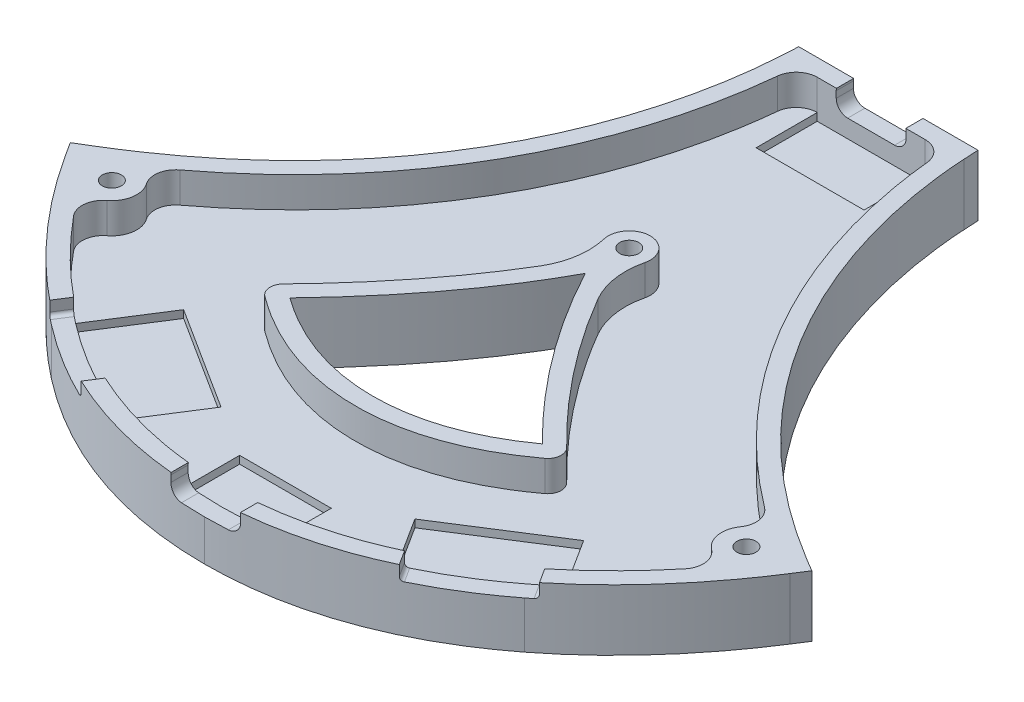
SolidWorks part; units mm, degrees
material "Default Heavy"
ref_plane "Front \"XY\"" through (0, 0, 0) normal (0, 0, 1) x (1, 0, 0)
ref_plane "Top \"XZ\"" through (0, 0, 0) normal (0, 1, 0) x (1, 0, 0)
ref_plane "Right \"YZ\"" through (0, 0, 0) normal (1, 0, 0) x (0, 0, -1)
sketch "Sketch5" plane through (0, 0, 0) normal (0, 1, 0) x (1, 0, 0)
  line L0 (11.8441, 37.7651) -> (11.7402, 39.6731)
  line L1 (11.7402, 39.6731) -> (-11.7315, 39.6731)
  line L2 (-11.7315, 39.6731) -> (-11.8354, 37.7651)
  line L3 (-46.7664, -17.8284) -> (-48.5396, -18.8969)
  line L4 (-48.5396, -18.8969) -> (-47.426, -20.6418)
  line L5 (47.433, -20.6463) -> (48.547, -18.9011)
  line L6 (48.547, -18.9011) -> (46.7735, -17.8326)
  line L7 (-6.0753, 35.6378) -> (7.9467, 35.6378)
  spline S0 degree 3 poles (46.7735, -17.8326) (17.0035, 0.1023) (12.4291, 27.0232) (11.8441, 37.7651) knots 0 0 0 0 1 1 1 1
  spline S1 degree 3 poles (-11.8354, 37.7651) (-12.42, 27.0256) (-16.9942, 0.1099) (-46.7664, -17.8284) knots 4 4 4 4 5 5 5 5
  spline S2 degree 3 poles (-47.426, -20.6418) (-44.2218, -25.663) (-38.764, -32.9144) (-30.9593, -38.9452) knots 7 7 7 7 8 8 8 8
  spline S3 degree 3 poles (-30.9593, -38.9452) (-21.5489, -46.2168) (-11.1312, -49.9039) (0.0044, -49.9039) knots 8 8 8 8 9 9 9 9
  spline S4 degree 3 poles (0.0044, -49.9039) (11.1376, -49.9039) (21.554, -46.2178) (30.9639, -38.9481) knots 9 9 9 9 10 10 10 10
  spline S5 degree 3 poles (30.9639, -38.9481) (38.7697, -32.9178) (44.2283, -25.667) (47.433, -20.6463) knots 10 10 10 10 11 11 11 11
  spline S6 degree 3 poles (-26.2671, -37.4303) (-33.7735, -32.2159) (-39.286, -25.5238) (-42.8998, -20.1821) knots 6 6 6 6 7 7 7 7
  spline S7 degree 3 poles (-21.0273, -20.9114) (-25.95, -25.8342) (-27.72, -31.5456) (-26.2671, -37.4303) knots 5 5 5 5 6 6 6 6
  spline S8 degree 3 poles (-2.2272, 4.5048) (-6.4059, -4.0601) (-12.7224, -12.6065) (-21.0273, -20.9114) knots 4 4 4 4 5 5 5 5
  spline S9 degree 3 poles (-4.959, 11.1576) (-4.2007, 9.0673) (-3.2985, 6.8364) (-2.2272, 4.5048) knots 3 3 3 3 4 4 4 4
  spline S10 degree 3 poles (-9.1537, 27.2693) (-8.3696, 22.4813) (-7.0743, 16.988) (-4.959, 11.1576) knots 2 2 2 2 3 3 3 3
  spline S11 degree 3 poles (-14.8927, 10.4237) (-11.9606, 16.4408) (-10.1982, 22.2166) (-9.1537, 27.2693) knots 1 1 1 1 2 2 2 2
  spline S12 degree 3 poles (-42.8998, -20.1821) (-30.3262, -12.2114) (-20.909, -1.9228) (-14.8927, 10.4237) knots 0 0 0 0 1 1 1 1
  spline S13 degree 3 poles (0, 0) (3.7422, -7.0613) (9.039, -14.7607) (16.5263, -22.1536) knots 3 3 3 3 4 4 4 4
  spline S14 degree 3 poles (-16.5604, -22.1226) (-9.5786, -14.8948) (-4.0267, -7.4755) (0, 0) knots 2 2 2 2 3 3 3 3
  spline S15 degree 3 poles (16.5263, -22.1536) (11.2873, -25.9276) (5.7395, -27.8446) (0.0044, -27.8446) (-5.7464, -27.8446) (-11.3088, -25.9169) (-16.5604, -22.1226) knots 0 0 0 0 1 1 1 2 2 2 2
  spline S16 degree 3 poles (30.8834, -33.8552) (23.2458, -40.4324) (13.0017, -45.8687) (0.0044, -45.8687) (-7.8162, -45.8687) (-14.6395, -43.9001) (-20.4984, -40.8995) knots 4 4 4 4 5 5 5 6 6 6 6
  spline S17 degree 3 poles (19.51, -24.974) (22.8871, -28.0328) (26.6618, -31.0165) (30.8834, -33.8552) knots 3 3 3 3 4 4 4 4
  spline S18 degree 3 poles (-19.372, -25.0702) (-13.2945, -29.589) (-6.7848, -31.8798) (0.0044, -31.8798) (6.8416, -31.8798) (13.3956, -29.5569) (19.51, -24.974) knots 1 1 1 1 2 2 2 3 3 3 3
  spline S19 degree 3 poles (-20.4984, -40.8995) (-23.8177, -35.2119) (-23.4372, -29.8962) (-19.372, -25.0702) knots 0 0 0 0 1 1 1 1
  spline S20 degree 3 poles (33.9362, -31.0385) (13.0256, -17.2626) (3.31, 0.1969) (-1.1657, 12.5337) knots 0 0 0 0 1 1 1 1
  spline S21 degree 3 poles (-1.1657, 12.5337) (-4.4547, 21.5995) (-5.6698, 29.8082) (-6.0753, 35.6378) knots 1 1 1 1 2 2 2 2
  spline S22 degree 3 poles (7.9467, 35.6378) (8.4835, 29.2105) (10.1709, 20.1275) (14.8992, 10.4216) knots 3 3 3 3 4 4 4 4
  spline S23 degree 3 poles (14.8992, 10.4216) (20.9146, -1.9265) (30.3319, -12.2156) (42.9069, -20.1863) knots 4 4 4 4 5 5 5 5
  spline S24 degree 3 poles (42.9069, -20.1863) (40.659, -23.5082) (37.6756, -27.3523) (33.9362, -31.0385) knots 5 5 5 5 6 6 6 6
sketch "Sketch10" plane through (0, 0, 0) normal (0, 1, 0) x (1, 0, 0)
  line L0 (48.547, -18.9011) -> (46.7735, -17.8326) construction
  line L1 (47.433, -20.6463) -> (48.547, -18.9011) construction
  line L2 (-48.5396, -18.8969) -> (-47.426, -20.6418) construction
  line L3 (-46.7664, -17.8284) -> (-48.5396, -18.8969) construction
  line L4 (-11.7315, 39.6731) -> (-11.8354, 37.7651) construction
  line L5 (11.7402, 39.6731) -> (-11.7315, 39.6731) construction
  line L6 (11.8441, 37.7651) -> (11.7402, 39.6731) construction
  line L14 (48.547, -18.9011) -> (46.7735, -17.8326)
  line L15 (47.433, -20.6463) -> (48.547, -18.9011)
  line L16 (-48.5396, -18.8969) -> (-47.426, -20.6418)
  line L17 (-46.7664, -17.8284) -> (-48.5396, -18.8969)
  line L18 (-11.7315, 39.6731) -> (-11.8354, 37.7651)
  line L19 (11.7402, 39.6731) -> (-11.7315, 39.6731)
  line L20 (11.8441, 37.7651) -> (11.7402, 39.6731)
  spline S0 degree 3 poles (-656.5291, 1825.394) (211.0906, -2141.3129) (197.0374, 2116.559) (-250.135, -1997.4745) knots 1.9887 1.9887 1.9887 1.9887 18.868565 18.868565 18.868565 18.868565 only from (30.9639, -38.9481) to (47.433, -20.6463) construction
  spline S1 degree 3 poles (-182.7302, 1911.4069) (-625.9753, -969.181) (972.7294, -384.9371) (-706.3522, 1782.3273) knots -3.602256 -3.602256 -3.602256 -3.602256 22.781955 22.781955 22.781955 22.781955 only from (0.0044, -49.9039) to (30.9639, -38.9481) construction
  spline S2 degree 3 poles (706.2836, 1782.3794) (-972.1545, -384.1805) (624.8527, -969.872) (184.0184, 1911.3649) knots -4.782528 -4.782528 -4.782528 -4.782528 21.598996 21.598996 21.598996 21.598996 only from (-30.9593, -38.9452) to (0.0044, -49.9039) construction
  spline S3 degree 3 poles (250.1669, -1997.4323) (-197.0811, 2116.5675) (-210.9874, -2141.3429) (656.3732, 1825.4364) knots -0.86853 -0.86853 -0.86853 -0.86853 16.011373 16.011373 16.011373 16.011373 only from (-47.426, -20.6418) to (-30.9593, -38.9452) construction
  spline S4 degree 3 poles (885.5961, -1747.6701) (-1144.1453, 1780.0004) (1414.1117, -1430.9185) (-1803.61, 911.43) knots 0.325017 0.325017 0.325017 0.325017 8.201625 8.201625 8.201625 8.201625 only from (-11.8354, 37.7651) to (-46.7664, -17.8284) construction
  spline S5 degree 3 poles (1803.2949, 912.0011) (-1413.7247, -1431.4451) (1143.7595, 1780.3831) (-885.202, -1747.8751) knots -3.201509 -3.201509 -3.201509 -3.201509 4.674641 4.674641 4.674641 4.674641 only from (46.7735, -17.8326) to (11.8441, 37.7651) construction
  spline S6 degree 3 poles (30.9639, -38.9481) (38.7697, -32.9178) (44.2283, -25.667) (47.433, -20.6463) knots 10 10 10 10 11 11 11 11
  spline S7 degree 3 poles (0.0044, -49.9039) (11.1376, -49.9039) (21.554, -46.2178) (30.9639, -38.9481) knots 9 9 9 9 10 10 10 10
  spline S8 degree 3 poles (-30.9593, -38.9452) (-21.5489, -46.2168) (-11.1312, -49.9039) (0.0044, -49.9039) knots 8 8 8 8 9 9 9 9
  spline S9 degree 3 poles (-47.426, -20.6418) (-44.2218, -25.663) (-38.764, -32.9144) (-30.9593, -38.9452) knots 7 7 7 7 8 8 8 8
  spline S10 degree 3 poles (-11.8354, 37.7651) (-12.42, 27.0256) (-16.9942, 0.1099) (-46.7664, -17.8284) knots 4 4 4 4 5 5 5 5
  spline S11 degree 3 poles (46.7735, -17.8326) (17.0035, 0.1023) (12.4291, 27.0232) (11.8441, 37.7651) knots 0 0 0 0 1 1 1 1
  spline S12 degree 3 poles (-812.1216, 1751.0499) (153.3939, 718.8091) (113.1908, -27.8446) (0.0044, -27.8446) (-113.2755, -27.8446) (-153.4167, 720.1128) (813.7688, 1750.0629) knots -18.735656 -18.735656 -18.735656 -18.735656 1 1 1 20.698036 20.698036 20.698036 20.698036 only from (16.5263, -22.1536) to (-16.5604, -22.1226) construction
  spline S13 degree 3 poles (-656.972, -1887.5112) (895.1742, 1891.164) (-1266.5252, -1556.179) (1736.0801, 959.1971) knots -9.517328 -9.517328 -9.517328 -9.517328 14.561888 14.561888 14.561888 14.561888 only from (0, 0) to (16.5263, -22.1536) construction
  spline S14 degree 3 poles (-1494.9401, 1101.9266) (-493.0371, -1467.4363) (1527.6763, 1113.0775) (-1935.6902, -378.8535) knots -19.400052 -19.400052 -19.400052 -19.400052 21.459168 21.459168 21.459168 21.459168 only from (-16.5604, -22.1226) to (0, 0) construction
  spline S15 degree 3 poles (16.5263, -22.1536) (11.2873, -25.9276) (5.7395, -27.8446) (0.0044, -27.8446) (-5.7464, -27.8446) (-11.3088, -25.9169) (-16.5604, -22.1226) knots 0 0 0 0 1 1 1 2 2 2 2
  spline S16 degree 3 poles (0, 0) (3.7422, -7.0613) (9.039, -14.7607) (16.5263, -22.1536) knots 3 3 3 3 4 4 4 4
  spline S17 degree 3 poles (-16.5604, -22.1226) (-9.5786, -14.8948) (-4.0267, -7.4755) (0, 0) knots 2 2 2 2 3 3 3 3
extrude "Boss-Extrude4" add sketch "Sketch10" along normal blind 3
hole_wizard "CBORE for M1.6 SHCS1" [suppressed] positions "Sketch13" profile "Sketch15" counterbore size "M1.6" standard "ANSI Metric"
sketch "Sketch13" plane through (0, 0, 0) normal (0, -1, 0) x (-1, 0, 0)
  point P0 (0, 3.0473)
  point P4 (0, -16.1117)
sketch "Sketch15" plane through (0, 0, -3.0473) normal (1, 0, 0) x (0, 0, -1)
  line L0 (0, 0) -> (0, 3)
  line L1 (0, 3) -> (0.9, 3)
  line L3 (0.9, 3) -> (0.9, 1.6)
  line L4 (0.9, 1.6) -> (1.75, 1.6)
  line L5 (1.75, 1.6) -> (1.75, 0)
  line L7 (1.75, 0) -> (0, 0)
  line L11 (0, -6.35) -> (0, 107.95) construction
  dimension "Thru Hole Dia." = 1.8
  dimension "Thru Hole Depth" = 3
  dimension "C'Bore Dia." = 3.5
  dimension "C'Bore Depth" = 1.6
sketch "Sketch16" plane through (0, 0, 0) normal (0, -1, 0) x (1, 0, 0)
  line L0 (0, 0) -> (0, 8.6371) construction
  line L2 (11.7402, -39.6731) -> (-11.7315, -39.6731) construction
  circle A0 centre (-41.547, 20.4011) radius 3.25
  circle A1 centre (41.547, 20.4011) radius 3.25
  circle A2 centre (0, -32.6731) radius 3.25
  circle A3 centre (0, 42.9039) radius 3.25
  dimension "D1" = 6.5
  dimension "D5" = 7
  dimension "D2" = 7
  dimension "D3" = 7
  dimension "D4" = 1.5
extrude "Cut-Extrude1" cut sketch "Sketch16" against normal blind 1.5
sketch "Sketch17" plane through (0, 3, 0) normal (0, 1, 0) x (1, 0, 0)
  line L0 (-45.0383, -19.5892) -> (-45.1073, -19.6307)
  line L1 (-45.1073, -19.6307) -> (-45.1073, -19.6307)
  line L2 (45.1144, -19.635) -> (45.1144, -19.635)
  line L3 (45.1144, -19.635) -> (45.0454, -19.5934)
  line L4 (9.4815, 37.0144) -> (9.4674, 37.2731)
  line L6 (-9.4586, 37.2731) -> (-9.4727, 37.0143)
  line L7 (47.433, -20.6463) -> (48.547, -18.9011) construction
  line L8 (-48.5396, -18.8969) -> (-47.426, -20.6418) construction
  line L9 (-46.7664, -17.8284) -> (-48.5396, -18.8969) construction
  line L10 (-11.7315, 39.6731) -> (-11.8354, 37.7651) construction
  line L11 (11.7402, 39.6731) -> (-11.7315, 39.6731) construction
  line L12 (11.8441, 37.7651) -> (11.7402, 39.6731) construction
  line L13 (48.547, -18.9011) -> (46.7735, -17.8326) construction
  line L14 (9.4674, 37.2731) -> (-9.4586, 37.2731) construction
  line L16 (47.433, -20.6463) -> (48.547, -18.9011)
  line L17 (-48.5396, -18.8969) -> (-47.426, -20.6418)
  line L18 (-46.7664, -17.8284) -> (-48.5396, -18.8969)
  line L19 (-11.7315, 39.6731) -> (-11.8354, 37.7651)
  line L20 (11.7402, 39.6731) -> (-11.7315, 39.6731)
  line L21 (11.8441, 37.7651) -> (11.7402, 39.6731)
  line L22 (48.547, -18.9011) -> (46.7735, -17.8326)
  line L23 (46.7735, -17.8326) -> (11.8441, 37.7651) construction
  line L24 (45.0454, -19.5934) -> (9.4815, 37.0144) construction
  line L25 (30.9639, -38.9481) -> (47.433, -20.6463) construction
  line L26 (29.588, -36.8891) -> (45.1144, -19.635) construction
  line L27 (0.0044, -49.9039) -> (30.9639, -38.9481) construction
  line L28 (0.0044, -47.3581) -> (29.588, -36.8891) construction
  line L29 (-30.9593, -38.9452) -> (0.0044, -49.9039) construction
  line L30 (-29.5833, -36.8863) -> (0.0044, -47.3581) construction
  line L31 (-47.426, -20.6418) -> (-30.9593, -38.9452) construction
  line L32 (-45.1073, -19.6307) -> (-29.5833, -36.8863) construction
  line L33 (-11.8354, 37.7651) -> (-46.7664, -17.8284) construction
  line L34 (-9.4727, 37.0143) -> (-45.0383, -19.5892) construction
  line L37 (7.0683, 37.4231) -> (-7.0595, 37.4231)
  line L38 (7.0683, 37.4231) -> (-7.0595, 37.4231)
  arc A42 (-38.2805, -14.817) -> (-38.8778, -18.5904) centre (-36.6252, -17.013) ccw
  arc A43 (-39.572, -23.0411) -> (-38.8778, -18.5904) centre (-41.54, -20.4546) ccw
  arc A44 (-39.572, -23.0411) -> (-40.0245, -26.984) centre (-37.9068, -25.2296) ccw
  arc A45 (40.0303, -26.9881) -> (39.5783, -23.0452) centre (37.9129, -25.2335) ccw
  arc A46 (38.8843, -18.595) -> (39.5783, -23.0452) centre (41.5466, -20.459) ccw
  arc A47 (38.8843, -18.595) -> (38.2869, -14.8218) centre (36.6316, -17.0178) ccw
  arc A48 (9.8049, 34.9434) -> (7.0683, 37.4231) centre (7.0683, 34.6731) ccw
  arc A49 (-7.0595, 37.4231) -> (-9.7962, 34.9434) centre (-7.0595, 34.6731) ccw
  arc A50 (-38.2805, -14.817) -> (-38.8778, -18.5904) centre (-36.6252, -17.013) ccw
  arc A51 (-39.572, -23.0411) -> (-38.8778, -18.5904) centre (-41.54, -20.4546) ccw
  arc A52 (-39.572, -23.0411) -> (-40.0245, -26.984) centre (-37.9068, -25.2296) ccw
  arc A53 (40.0303, -26.9881) -> (39.5783, -23.0452) centre (37.9129, -25.2335) ccw
  arc A54 (38.8843, -18.595) -> (39.5783, -23.0452) centre (41.5466, -20.459) ccw
  arc A55 (38.8843, -18.595) -> (38.2869, -14.8218) centre (36.6316, -17.0178) ccw
  arc A56 (9.8049, 34.9434) -> (7.0683, 37.4231) centre (7.0683, 34.6731) ccw
  arc A57 (-7.0595, 37.4231) -> (-9.7962, 34.9434) centre (-7.0595, 34.6731) ccw
  arc A60 (-18.5797, -20.9745) -> (-18.348, -23.6073) centre (-17.321, -22.1903) ccw
  arc A61 (18.3239, -23.6323) -> (18.5285, -20.9686) centre (17.2989, -22.2139) ccw
  arc A62 (2.674, 5.108) -> (3.7352, -2.0849) centre (12.1546, 2.832) ccw
  arc A63 (2.674, 5.108) -> (-2.6765, 5.1183) centre (0, 5.75) ccw
  arc A64 (-3.8051, -2.1373) -> (-2.6765, 5.1183) centre (-12.1658, 2.8788) ccw
  arc A65 (-18.5797, -20.9745) -> (-18.348, -23.6073) centre (-17.321, -22.1903) ccw
  arc A66 (18.3239, -23.6323) -> (18.5285, -20.9686) centre (17.2989, -22.2139) ccw
  arc A67 (2.674, 5.108) -> (3.7352, -2.0849) centre (12.1546, 2.832) ccw
  arc A68 (2.674, 5.108) -> (-2.6765, 5.1183) centre (0, 5.75) ccw
  arc A69 (-3.8051, -2.1373) -> (-2.6765, 5.1183) centre (-12.1658, 2.8788) ccw
  spline S6 degree 3 poles (-656.5291, 1825.394) (211.0906, -2141.3129) (197.0374, 2116.559) (-250.135, -1997.4745) knots 1.9887 1.9887 1.9887 1.9887 18.868565 18.868565 18.868565 18.868565 only from (30.9639, -38.9481) to (47.433, -20.6463) construction
  spline S7 degree 3 poles (-182.7302, 1911.4069) (-625.9753, -969.181) (972.7294, -384.9371) (-706.3522, 1782.3273) knots -3.602256 -3.602256 -3.602256 -3.602256 22.781955 22.781955 22.781955 22.781955 only from (0.0044, -49.9039) to (30.9639, -38.9481) construction
  spline S8 degree 3 poles (706.2836, 1782.3794) (-972.1545, -384.1805) (624.8527, -969.872) (184.0184, 1911.3649) knots -4.782528 -4.782528 -4.782528 -4.782528 21.598996 21.598996 21.598996 21.598996 only from (-30.9593, -38.9452) to (0.0044, -49.9039) construction
  spline S9 degree 3 poles (250.1669, -1997.4323) (-197.0811, 2116.5675) (-210.9874, -2141.3429) (656.3732, 1825.4364) knots -0.86853 -0.86853 -0.86853 -0.86853 16.011373 16.011373 16.011373 16.011373 only from (-47.426, -20.6418) to (-30.9593, -38.9452) construction
  spline S10 degree 3 poles (885.5961, -1747.6701) (-1144.1453, 1780.0004) (1414.1117, -1430.9185) (-1803.61, 911.43) knots 0.325017 0.325017 0.325017 0.325017 8.201625 8.201625 8.201625 8.201625 only from (-11.8354, 37.7651) to (-46.7664, -17.8284) construction
  spline S11 degree 3 poles (1803.2949, 912.0011) (-1413.7247, -1431.4451) (1143.7595, 1780.3831) (-885.202, -1747.8751) knots -3.201509 -3.201509 -3.201509 -3.201509 4.674641 4.674641 4.674641 4.674641 only from (46.7735, -17.8326) to (11.8441, 37.7651) construction
  spline S18 degree 3 poles (-8502.8403, -15893.4352) (-45.3248, 163.6482) (-63.6079, 7.9202) (-16.9995, -24.5656) (-16.6575, -24.7958) (-15.6219, -25.4682) (-14.9188, -25.892) (-12.7682, -27.0849) (-11.2799, -27.7756) (-8.9522, -28.6296) (-8.1568, -28.8845) (-6.5604, -29.3207) (-5.7573, -29.503) (-3.3327, -29.9425) (-1.6963, -30.092) (0.7891, -30.0958) (1.6234, -30.0599) (3.2688, -29.9148) (4.0842, -29.8058) (6.5087, -29.3724) (8.0964, -28.9415) (10.4366, -28.0907) (11.2058, -27.7741) (12.7076, -27.0863) (13.4428, -26.7142) (14.8841, -25.9177) (15.5903, -25.4934) (16.6293, -24.8206) (16.9723, -24.5902) (63.7168, 7.9132) (43.0919, 160.7438) (8908.8285, -15669.934) knots -4.23549 -4.23549 -4.23549 -4.23549 0.03125 0.03125 0.0625 0.0625 0.125 0.125 0.25 0.25 0.3125 0.3125 0.375 0.375 0.5 0.5 0.5625 0.5625 0.625 0.625 0.75 0.75 0.8125 0.8125 0.875 0.875 0.9375 0.9375 0.96875 0.96875 5.237555 5.237555 5.237555 5.237555 only from (-18.348, -23.6073) to (18.3239, -23.6323)
  spline S19 degree 3 poles (-12741.1091, -12700.2374) (334.5389, -8.3643) (90.0879, -95.516) (15.7148, -18.1086) (15.0318, -17.374) (13.0192, -15.1354) (11.7285, -13.5998) (-271.5891, 347.605) (2349.0319, 2696.4064) (15492.6273, 8956.8904) knots -13.129152 -13.129152 -13.129152 -13.129152 0.125 0.125 0.25 0.25 0.5 0.5 57.436471 57.436471 57.436471 57.436471 only from (18.5285, -20.9686) to (3.7352, -2.0849)
  spline S20 degree 3 poles (-17058.6487, 5589.1782) (-397.9032, 918.6322) (143.7118, 183.0534) (-11.892, -13.5529) (-13.1768, -15.0838) (-15.1614, -17.3294) (-15.8326, -18.0695) (-96.5644, -104.9378) (-336.1354, -50.3454) (13236.7022, -12181.1124) knots -30.580141 -30.580141 -30.580141 -30.580141 0.5 0.5 0.75 0.75 0.875 0.875 15.584267 15.584267 15.584267 15.584267 only from (-3.8051, -2.1373) to (-18.5797, -20.9745)
  spline S21 degree 3 poles (-18.348, -23.6073) (-18.0127, -23.8503) (-17.6773, -24.0932) (-16.9995, -24.5656) (-16.6575, -24.7958) (-15.6219, -25.4682) (-14.9188, -25.892) (-12.7682, -27.0849) (-11.2799, -27.7756) (-8.9522, -28.6296) (-8.1568, -28.8845) (-6.5604, -29.3207) (-5.7573, -29.503) (-3.3327, -29.9425) (-1.6963, -30.092) (0.7891, -30.0958) (1.6234, -30.0599) (3.2688, -29.9148) (4.0842, -29.8058) (6.5087, -29.3724) (8.0964, -28.9415) (10.4366, -28.0907) (11.2058, -27.7741) (12.7076, -27.0863) (13.4428, -26.7142) (14.8841, -25.9177) (15.5903, -25.4934) (16.6293, -24.8206) (16.9723, -24.5902) (17.6517, -24.1178) (17.9878, -23.8751) (18.3239, -23.6323) knots 0 0 0 0 0.03125 0.03125 0.0625 0.0625 0.125 0.125 0.25 0.25 0.3125 0.3125 0.375 0.375 0.5 0.5 0.5625 0.5625 0.625 0.625 0.75 0.75 0.8125 0.8125 0.875 0.875 0.9375 0.9375 0.96875 0.96875 1 1 1 1
  spline S22 degree 3 poles (18.5285, -20.9686) (17.8145, -20.2637) (17.1045, -19.555) (15.7148, -18.1086) (15.0318, -17.374) (13.0192, -15.1354) (11.7285, -13.5998) (8.0128, -8.8627) (5.7595, -5.5511) (3.7352, -2.0849) knots 0 0 0 0 0.125 0.125 0.25 0.25 0.5 0.5 1 1 1 1
  spline S23 degree 3 poles (-3.8051, -2.1373) (-5.8639, -5.5689) (-8.1671, -8.8465) (-11.892, -13.5529) (-13.1768, -15.0838) (-15.1614, -17.3294) (-15.8326, -18.0695) (-17.1931, -19.5335) (-17.8849, -20.2553) (-18.5797, -20.9745) knots 0 0 0 0 0.5 0.5 0.75 0.75 0.875 0.875 1 1 1 1
  spline S24 degree 3 poles (30.9639, -38.9481) (38.7697, -32.9178) (44.2283, -25.667) (47.433, -20.6463) knots 10 10 10 10 11 11 11 11
  spline S25 degree 3 poles (0.0044, -49.9039) (11.1376, -49.9039) (21.554, -46.2178) (30.9639, -38.9481) knots 9 9 9 9 10 10 10 10
  spline S26 degree 3 poles (-30.9593, -38.9452) (-21.5489, -46.2168) (-11.1312, -49.9039) (0.0044, -49.9039) knots 8 8 8 8 9 9 9 9
  spline S27 degree 3 poles (-47.426, -20.6418) (-44.2218, -25.663) (-38.764, -32.9144) (-30.9593, -38.9452) knots 7 7 7 7 8 8 8 8
  spline S28 degree 3 poles (-11.8354, 37.7651) (-12.42, 27.0256) (-16.9942, 0.1099) (-46.7664, -17.8284) knots 4 4 4 4 5 5 5 5
  spline S29 degree 3 poles (46.7735, -17.8326) (17.0035, 0.1023) (12.4291, 27.0232) (11.8441, 37.7651) knots 0 0 0 0 1 1 1 1
  spline S30 degree 3 poles (-1185.458, -17971.1401) (732.7038, 1486.4598) (-227.1134, 155.6968) (126.3209, -190.4314) (1044.5984, 512.9613) (11833.1848, 13466.1097) knots -54.647972 -54.647972 -54.647972 -54.647972 0.5 0.5 46.852212 46.852212 46.852212 46.852212 only from (-40.0245, -26.984) to (-29.5836, -37.1648)
  spline S31 degree 3 poles (-10552.0267, -14577.9353) (551.6703, 1727.3625) (-240.731, 80.6268) (-20.5651, -42.9151) (-18.1378, -44.0356) (-13.0925, -45.8527) (-10.5261, -46.5302) (665.8325, -163.4732) (3949.6007, 14900.1764) (343.1731, -10110.3603) knots -23.042965 -23.042965 -23.042965 -23.042965 0.25 0.25 0.5 0.5 0.75 0.75 65.44657 65.44657 65.44657 65.44657 only from (-29.5836, -37.1648) to (0.0044, -47.6539)
  spline S32 degree 3 poles (498.348, -17908.4467) (-1031.6717, 3878.1158) (-337.2571, -107.1241) (10.6298, -46.5101) (13.1926, -45.8231) (16.9224, -44.4744) (18.1468, -43.9718) (20.5589, -42.863) (21.7488, -42.2556) (241.5188, 81.0938) (-552.0997, 1742.02) (10508.6827, -14611.7053) knots -32.427338 -32.427338 -32.427338 -32.427338 0.25 0.25 0.5 0.5 0.625 0.625 0.75 0.75 24.161666 24.161666 24.161666 24.161666 only from (0.0044, -47.6539) to (29.5883, -37.1675)
  spline S33 degree 3 poles (-4432.1105, 17338.2057) (-1006.9632, 428.8583) (-119.8702, -184.1086) (246.2577, 174.4174) (-984.7381, 1707.4439) (13684.8963, -11666.0569) knots -44.001228 -44.001228 -44.001228 -44.001228 0.5 0.5 61.1418 61.1418 61.1418 61.1418 only from (29.5883, -37.1675) to (40.0303, -26.9881)
  spline S34 degree 3 poles (-11165.7487, -13920.1383) (2728.7098, 1775.4972) (290.1282, -298.2618) (26.5572, -3.9157) (25.7572, -2.9746) (24.2132, -1.06) (23.4685, -0.0857) (21.3159, 2.8881) (19.9895, 4.9384) (17.5545, 9.1749) (16.4462, 11.3612) (14.9506, 14.7449) (14.479, 15.893) (13.6014, 18.201) (13.1943, 19.363) (12.0661, 22.8721) (11.4377, 25.2424) (-38.013, 260.9023) (1069.2526, 782.7681) (17262.5755, 5070.3319) knots -19.636593 -19.636593 -19.636593 -19.636593 0.25 0.25 0.3125 0.3125 0.375 0.375 0.5 0.5 0.625 0.625 0.6875 0.6875 0.75 0.75 0.875 0.875 13.016987 13.016987 13.016987 13.016987 only from (38.2869, -14.8218) to (9.8049, 34.9434)
  spline S35 degree 3 poles (-17418.867, 4498.5821) (-1179.3159, 784.7283) (40.1821, 270.8316) (-11.4341, 25.2229) (-12.0664, 22.8402) (-13.2054, 19.3068) (-13.6155, 18.1405) (-14.492, 15.8418) (-14.959, 14.7077) (-16.4453, 11.3505) (-17.5494, 9.1724) (-19.985, 4.9365) (-21.3163, 2.8786) (-23.4866, -0.1162) (-24.2409, -1.1014) (-25.7928, -3.0222) (-26.5915, -3.9596) (-307.7012, -317.3915) (-3147.3468, 1971.0689) (11546.2104, -13558.8019) knots -12.491721 -12.491721 -12.491721 -12.491721 0.125 0.125 0.25 0.25 0.3125 0.3125 0.375 0.375 0.5 0.5 0.625 0.625 0.6875 0.6875 0.75 0.75 22.097055 22.097055 22.097055 22.097055 only from (-9.7962, 34.9434) to (-38.2805, -14.817)
  spline S36 degree 3 poles (-40.0245, -26.984) (-38.4698, -28.8606) (-36.8234, -30.6596) (-33.3413, -34.0697) (-31.5122, -35.6745) (-29.5836, -37.1648) knots 0 0 0 0 0.5 0.5 1 1 1 1
  spline S37 degree 3 poles (-29.5836, -37.1648) (-27.4624, -38.8038) (-25.2409, -40.2913) (-20.5651, -42.9151) (-18.1378, -44.0356) (-13.0925, -45.8527) (-10.5261, -46.5302) (-5.319, -47.4305) (-2.6765, -47.6539) (0.0044, -47.6539) knots 0 0 0 0 0.25 0.25 0.5 0.5 0.75 0.75 1 1 1 1
  spline S38 degree 3 poles (0.0044, -47.6539) (2.6854, -47.6539) (5.3472, -47.4305) (10.6298, -46.5101) (13.1926, -45.8231) (16.9224, -44.4744) (18.1468, -43.9718) (20.5589, -42.863) (21.7488, -42.2556) (25.2503, -40.2903) (27.4692, -38.8047) (29.5883, -37.1675) knots 0 0 0 0 0.25 0.25 0.5 0.5 0.625 0.625 0.75 0.75 1 1 1 1
  spline S39 degree 3 poles (29.5883, -37.1675) (31.5168, -35.6777) (33.3504, -34.0693) (36.8326, -30.6594) (38.4756, -28.8643) (40.0303, -26.9881) knots 0 0 0 0 0.5 0.5 1 1 1 1
  spline S40 degree 3 poles (38.2869, -14.8218) (34.3329, -11.8412) (30.686, -8.5266) (26.5572, -3.9157) (25.7572, -2.9746) (24.2132, -1.06) (23.4685, -0.0857) (21.3159, 2.8881) (19.9895, 4.9384) (17.5545, 9.1749) (16.4462, 11.3612) (14.9506, 14.7449) (14.479, 15.893) (13.6014, 18.201) (13.1943, 19.363) (12.0661, 22.8721) (11.4377, 25.2424) (10.4299, 30.0451) (10.0486, 32.4771) (9.8049, 34.9434) knots 0 0 0 0 0.25 0.25 0.3125 0.3125 0.375 0.375 0.5 0.5 0.625 0.625 0.6875 0.6875 0.75 0.75 0.875 0.875 1 1 1 1
  spline S41 degree 3 poles (-9.7962, 34.9434) (-10.0397, 32.4779) (-10.4214, 30.0419) (-11.4341, 25.2229) (-12.0664, 22.8402) (-13.2054, 19.3068) (-13.6155, 18.1405) (-14.492, 15.8418) (-14.959, 14.7077) (-16.4453, 11.3505) (-17.5494, 9.1724) (-19.985, 4.9365) (-21.3163, 2.8786) (-23.4866, -0.1162) (-24.2409, -1.1014) (-25.7928, -3.0222) (-26.5915, -3.9596) (-30.6946, -8.5345) (-34.3282, -11.8377) (-38.2805, -14.817) knots 0 0 0 0 0.125 0.125 0.25 0.25 0.3125 0.3125 0.375 0.375 0.5 0.5 0.625 0.625 0.6875 0.6875 0.75 0.75 1 1 1 1
  spline S53 degree 3 poles (-1935.686, -378.8517) (1527.6682, 1113.0726) (-493.0299, -1467.4256) (-1494.9344, 1101.9122) knots -16.459151 -16.459151 -16.459151 -16.459151 24.399976 24.399976 24.399976 24.399976 only from (0, 0) to (-16.5604, -22.1226) construction
  spline S54 degree 3 poles (1736.0666, 959.1858) (-1266.5041, -1556.1565) (895.1508, 1891.1248) (-656.9493, -1887.456) knots -7.561852 -7.561852 -7.561852 -7.561852 16.517211 16.517211 16.517211 16.517211 only from (16.5263, -22.1536) to (0, 0) construction
  spline S55 degree 3 poles (813.7576, 1750.051) (-153.4164, 720.107) (-113.2751, -27.8446) (0.0044, -27.8446) (113.1912, -27.8446) (153.3942, 718.8147) (-812.1324, 1751.0615) knots -18.697961 -18.697961 -18.697961 -18.697961 1 1 1 20.73573 20.73573 20.73573 20.73573 only from (-16.5604, -22.1226) to (16.5263, -22.1536) construction
  spline S62 degree 3 poles (0, 0) (-4.0267, -7.4755) (-9.5786, -14.8948) (-16.5604, -22.1226) knots 2 2 2 2 3 3 3 3
  spline S63 degree 3 poles (16.5263, -22.1536) (9.039, -14.7607) (3.7422, -7.0613) (0, 0) knots 3 3 3 3 4 4 4 4
  spline S64 degree 3 poles (-16.5604, -22.1226) (-11.3088, -25.9169) (-5.7464, -27.8446) (0.0044, -27.8446) (5.7395, -27.8446) (11.2873, -25.9276) (16.5263, -22.1536) knots 0 0 0 0 1 1 1 2 2 2 2
  dimension "D3" = 0.25
  dimension "D1" = 2.4
  dimension "D2" = 0.25
extrude "Boss-Extrude5" add sketch "Sketch17" along normal blind 5
hole_wizard "CBORE for M2 SHCS1" positions "Sketch32" profile "Sketch33" counterbore size "M2" standard "ANSI Metric" end condition up to next
sketch "Sketch32" plane through (0, 1.5, 0) normal (0, 1, 0) x (1, 0, 0)
  point P36 (-41.54, -20.4546)
  point P42 (41.5466, -20.459)
sketch "Sketch33" plane through (-41.54, 1.5, 20.4546) normal (1, 0, 0) x (0, 0, -1)
  line L0 (0, 0) -> (0, 6.5)
  line L1 (0, 6.5) -> (1.25, 6.5)
  line L3 (1.25, 6.5) -> (1.25, 2.75)
  line L4 (1.25, 2.75) -> (2.2, 2.75)
  line L5 (2.2, 2.75) -> (2.2, 0)
  line L7 (2.2, 0) -> (0, 0)
  line L11 (0, -6.35) -> (0, 107.95) construction
  dimension "Thru Hole Dia." = 2.5
  dimension "Thru Hole Depth" = 6.5
  dimension "C'Bore Dia." = 4.4
  dimension "C'Bore Depth" = 2.75
hole_wizard "CBORE for M2 SHCS2" positions "Sketch34" profile "Sketch35" counterbore size "M2" standard "ANSI Metric" end condition up to next
sketch "Sketch34" plane through (0, 0, 0) normal (0, -1, 0) x (-1, 0, 0)
  point P5 (0, 5.75)
sketch "Sketch35" plane through (0, 0, -5.75) normal (1, 0, 0) x (0, 0, -1)
  line L0 (0, 0) -> (0, 8)
  line L1 (0, 8) -> (1.25, 8)
  line L3 (1.25, 8) -> (1.25, 2.75)
  line L4 (1.25, 2.75) -> (2.2, 2.75)
  line L5 (2.2, 2.75) -> (2.2, 0)
  line L7 (2.2, 0) -> (0, 0)
  line L11 (0, -6.35) -> (0, 107.95) construction
  dimension "Thru Hole Dia." = 2.5
  dimension "Thru Hole Depth" = 8
  dimension "C'Bore Dia." = 4.4
  dimension "C'Bore Depth" = 2.75
sketch "Sketch30" plane through (0, 3, 0) normal (0, 1, 0) x (1, 0, 0)
  line L0 (-26.183, -26.4172) -> (-12.6887, -35.0139)
  line L1 (-7.0595, 37.4231) -> (-7.0595, 29.4231)
  line L4 (7.0683, 37.4231) -> (-7.0595, 37.4231)
  line L6 (-7.0595, 29.4231) -> (7.0683, 29.4231)
  line L7 (7.0683, 29.4231) -> (7.0683, 37.4231)
  line L8 (-5.9956, -39.2712) -> (-5.9956, -47.2712)
  line L9 (6.0044, -39.2712) -> (6.0044, -47.2712)
  line L10 (-31.8544, -35.3194) -> (-26.183, -26.4172)
  line L11 (-18.3304, -43.8696) -> (-12.6887, -35.0139)
  line L12 (18.3391, -43.8693) -> (12.6974, -35.0137)
  line L13 (31.8631, -35.3192) -> (26.1917, -26.4169)
  line L14 (-5.9956, -39.2712) -> (6.0044, -39.2712)
  line L15 (25.2885, -39.8885) -> (20.9901, -33.1413) construction
  line L16 (12.6974, -35.0137) -> (26.1917, -26.4169)
  line L19 (-25.2799, -39.8888) -> (-20.9815, -33.1417) construction
  arc A10 (-18.5797, -20.9745) -> (-18.348, -23.6073) centre (-17.321, -22.1903) ccw construction
  arc A18 (18.3239, -23.6323) -> (18.5285, -20.9686) centre (17.2989, -22.2139) ccw construction
  arc A25 (-7.0595, 37.4231) -> (-9.7962, 34.9434) centre (-7.0595, 34.6731) ccw
  arc A26 (-38.2805, -14.817) -> (-38.8778, -18.5904) centre (-36.6252, -17.013) ccw
  arc A27 (-39.572, -23.0411) -> (-38.8778, -18.5904) centre (-41.54, -20.4546) ccw
  arc A28 (-39.572, -23.0411) -> (-40.0245, -26.984) centre (-37.9068, -25.2296) ccw
  arc A29 (40.0303, -26.9881) -> (39.5783, -23.0452) centre (37.9129, -25.2335) ccw
  arc A30 (38.8843, -18.595) -> (39.5783, -23.0452) centre (41.5466, -20.459) ccw
  arc A31 (38.8843, -18.595) -> (38.2869, -14.8218) centre (36.6316, -17.0178) ccw
  arc A32 (9.8049, 34.9434) -> (7.0683, 37.4231) centre (7.0683, 34.6731) ccw
  arc A33 (-7.0595, 37.4231) -> (-9.7962, 34.9434) centre (-7.0595, 34.6731) ccw
  arc A34 (-38.2805, -14.817) -> (-38.8778, -18.5904) centre (-36.6252, -17.013) ccw
  arc A35 (-39.572, -23.0411) -> (-38.8778, -18.5904) centre (-41.54, -20.4546) ccw
  arc A36 (-39.572, -23.0411) -> (-40.0245, -26.984) centre (-37.9068, -25.2296) ccw
  arc A37 (40.0303, -26.9881) -> (39.5783, -23.0452) centre (37.9129, -25.2335) ccw
  arc A38 (38.8843, -18.595) -> (39.5783, -23.0452) centre (41.5466, -20.459) ccw
  arc A39 (38.8843, -18.595) -> (38.2869, -14.8218) centre (36.6316, -17.0178) ccw
  arc A40 (9.8049, 34.9434) -> (7.0683, 37.4231) centre (7.0683, 34.6731) ccw
  arc A41 (2.674, 5.108) -> (3.7352, -2.0849) centre (12.1546, 2.832) ccw construction
  arc A42 (2.674, 5.108) -> (-2.6765, 5.1183) centre (0, 5.75) ccw construction
  arc A43 (-3.8051, -2.1373) -> (-2.6765, 5.1183) centre (-12.1658, 2.8788) ccw construction
  arc A44 (-18.5797, -20.9745) -> (-18.348, -23.6073) centre (-17.321, -22.1903) ccw
  arc A45 (18.3239, -23.6323) -> (18.5285, -20.9686) centre (17.2989, -22.2139) ccw
  arc A46 (2.674, 5.108) -> (3.7352, -2.0849) centre (12.1546, 2.832) ccw
  arc A47 (2.674, 5.108) -> (-2.6765, 5.1183) centre (0, 5.75) ccw
  arc A48 (-3.8051, -2.1373) -> (-2.6765, 5.1183) centre (-12.1658, 2.8788) ccw
  spline S0 degree 3 poles (-40.0245, -26.984) (-38.4698, -28.8606) (-36.8234, -30.6596) (-33.3413, -34.0697) (-31.5122, -35.6745) (-29.5836, -37.1648) knots 0 0 0 0 0.5 0.5 1 1 1 1 construction
  spline S2 degree 3 poles (-1015.0039, -1756.905) (-47.0433, 36.0466) (-39.7913, -8.6798) (-16.9995, -24.5656) (-16.6575, -24.7958) (-15.6219, -25.4682) (-14.9188, -25.892) (-12.7682, -27.0849) (-11.2799, -27.7756) (-8.9522, -28.6296) (-8.1568, -28.8845) (-6.5604, -29.3207) (-5.7573, -29.503) (-3.3327, -29.9425) (-1.6963, -30.092) (0.7891, -30.0958) (1.6234, -30.0599) (3.2688, -29.9148) (4.0842, -29.8058) (6.5087, -29.3724) (8.0964, -28.9415) (10.4366, -28.0907) (11.2058, -27.7741) (12.7076, -27.0863) (13.4428, -26.7142) (14.8841, -25.9177) (15.5903, -25.4934) (16.6293, -24.8206) (16.9723, -24.5902) (39.8223, -8.7017) (46.56, 35.3203) (1059.5079, -1730.484) knots -2.039245 -2.039245 -2.039245 -2.039245 0.03125 0.03125 0.0625 0.0625 0.125 0.125 0.25 0.25 0.3125 0.3125 0.375 0.375 0.5 0.5 0.5625 0.5625 0.625 0.625 0.75 0.75 0.8125 0.8125 0.875 0.875 0.9375 0.9375 0.96875 0.96875 3.039487 3.039487 3.039487 3.039487 only from (-18.348, -23.6073) to (18.3239, -23.6323) construction
  spline S6 degree 3 poles (-1313.4457, -1510.0135) (128.7022, -54.6649) (52.2975, -56.1838) (15.7148, -18.1086) (15.0318, -17.374) (13.0192, -15.1354) (11.7285, -13.5998) (-98.0603, 126.3712) (223.2447, 559.3363) (1408.6657, 1396.4335) knots -6.330954 -6.330954 -6.330954 -6.330954 0.125 0.125 0.25 0.25 0.5 0.5 22.410413 22.410413 22.410413 22.410413 only from (18.5285, -20.9686) to (3.7352, -2.0849) construction
  spline S10 degree 3 poles (-1755.9749, 936.4583) (-16.3572, 283.0343) (60.5657, 77.9978) (-11.892, -13.5529) (-13.1768, -15.0838) (-15.1614, -17.3294) (-15.8326, -18.0695) (-55.4601, -60.7091) (-132.1668, -69.3051) (1362.4419, -1464.1216) knots -13.839049 -13.839049 -13.839049 -13.839049 0.5 0.5 0.75 0.75 0.875 0.875 8.031451 8.031451 8.031451 8.031451 only from (-3.8051, -2.1373) to (-18.5797, -20.9745) construction
  spline S14 degree 3 poles (-18.348, -23.6073) (-18.0127, -23.8503) (-17.6773, -24.0932) (-16.9995, -24.5656) (-16.6575, -24.7958) (-15.6219, -25.4682) (-14.9188, -25.892) (-12.7682, -27.0849) (-11.2799, -27.7756) (-8.9522, -28.6296) (-8.1568, -28.8845) (-6.5604, -29.3207) (-5.7573, -29.503) (-3.3327, -29.9425) (-1.6963, -30.092) (0.7891, -30.0958) (1.6234, -30.0599) (3.2688, -29.9148) (4.0842, -29.8058) (6.5087, -29.3724) (8.0964, -28.9415) (10.4366, -28.0907) (11.2058, -27.7741) (12.7076, -27.0863) (13.4428, -26.7142) (14.8841, -25.9177) (15.5903, -25.4934) (16.6293, -24.8206) (16.9723, -24.5902) (17.6517, -24.1178) (17.9878, -23.8751) (18.3239, -23.6323) knots 0 0 0 0 0.03125 0.03125 0.0625 0.0625 0.125 0.125 0.25 0.25 0.3125 0.3125 0.375 0.375 0.5 0.5 0.5625 0.5625 0.625 0.625 0.75 0.75 0.8125 0.8125 0.875 0.875 0.9375 0.9375 0.96875 0.96875 1 1 1 1
  spline S15 degree 3 poles (18.5285, -20.9686) (17.8145, -20.2637) (17.1045, -19.555) (15.7148, -18.1086) (15.0318, -17.374) (13.0192, -15.1354) (11.7285, -13.5998) (8.0128, -8.8627) (5.7595, -5.5511) (3.7352, -2.0849) knots 0 0 0 0 0.125 0.125 0.25 0.25 0.5 0.5 1 1 1 1
  spline S16 degree 3 poles (-3.8051, -2.1373) (-5.8639, -5.5689) (-8.1671, -8.8465) (-11.892, -13.5529) (-13.1768, -15.0838) (-15.1614, -17.3294) (-15.8326, -18.0695) (-17.1931, -19.5335) (-17.8849, -20.2553) (-18.5797, -20.9745) knots 0 0 0 0 0.5 0.5 0.75 0.75 0.875 0.875 1 1 1 1
  spline S17 degree 3 poles (-2831.4338, 1021.6346) (-296.1366, 350.4653) (15.43, 153.0522) (-11.4341, 25.2229) (-12.0664, 22.8402) (-13.2054, 19.3068) (-13.6155, 18.1405) (-14.492, 15.8418) (-14.959, 14.7077) (-16.4453, 11.3505) (-17.5494, 9.1724) (-19.985, 4.9365) (-21.3163, 2.8786) (-23.4866, -0.1162) (-24.2409, -1.1014) (-25.7928, -3.0222) (-26.5915, -3.9596) (-202.9113, -200.5528) (-1381.7981, 623.4738) (1368.1442, -2545.22) knots -6.381546 -6.381546 -6.381546 -6.381546 0.125 0.125 0.25 0.25 0.3125 0.3125 0.375 0.375 0.5 0.5 0.625 0.625 0.6875 0.6875 0.75 0.75 14.116169 14.116169 14.116169 14.116169 only from (-9.7962, 34.9434) to (-38.2805, -14.817)
  spline S18 degree 3 poles (-0.2482, -3023.3672) (139.9727, 588.548) (-148.5171, 78.7252) (49.0502, -114.7581) (338.8324, 36.9148) (2125.0022, 2035.5813) knots -32.076484 -32.076484 -32.076484 -32.076484 0.5 0.5 24.661422 24.661422 24.661422 24.661422 only from (-40.0245, -26.984) to (-29.5836, -37.1648)
  spline S19 degree 3 poles (-2017.3383, -2251.4823) (72.6642, 635.8553) (-151.6927, 30.6647) (-20.5651, -42.9151) (-18.1378, -44.0356) (-13.0925, -45.8527) (-10.5261, -46.5302) (209.11, -84.5055) (696.9673, 1453.1179) (1138.107, 2719.0263) knots -13.521852 -13.521852 -13.521852 -13.521852 0.25 0.25 0.5 0.5 0.75 0.75 21.590306 21.590306 21.590306 21.590306 only from (-29.5836, -37.1648) to (0.0044, -47.6539)
  spline S20 degree 3 poles (-411.7947, -2939.3395) (-573.261, 1516.6686) (-211.8492, -85.2737) (10.6298, -46.5101) (13.1926, -45.8231) (16.9224, -44.4744) (18.1468, -43.9718) (20.5589, -42.863) (21.7488, -42.2556) (152.2272, 30.9775) (-72.6517, 641.8039) (2011.4931, -2256.2991) knots -20.557539 -20.557539 -20.557539 -20.557539 0.25 0.25 0.5 0.5 0.625 0.625 0.75 0.75 14.598821 14.598821 14.598821 14.598821 only from (0.0044, -47.6539) to (29.5883, -37.1675)
  spline S21 degree 3 poles (-1106.9435, 2717.4208) (-337.2919, 22.7489) (-47.3899, -113.1331) (160.4676, 90.4086) (-222.544, 680.7065) (2515.9224, -1659.0082) knots -23.186642 -23.186642 -23.186642 -23.186642 0.5 0.5 36.504982 36.504982 36.504982 36.504982 only from (29.5883, -37.1675) to (40.0303, -26.9881)
  spline S22 degree 3 poles (-1353.1781, -2579.6671) (1181.0742, 535.0713) (189.5906, -185.9853) (26.5572, -3.9157) (25.7572, -2.9746) (24.2132, -1.06) (23.4685, -0.0857) (21.3159, 2.8881) (19.9895, 4.9384) (17.5545, 9.1749) (16.4462, 11.3612) (14.9506, 14.7449) (14.479, 15.893) (13.6014, 18.201) (13.1943, 19.363) (12.0661, 22.8721) (11.4377, 25.2424) (-14.4197, 148.4673) (270.4437, 346.7254) (2801.4472, 1105.6526) knots -12.027129 -12.027129 -12.027129 -12.027129 0.25 0.25 0.3125 0.3125 0.375 0.375 0.5 0.5 0.625 0.625 0.6875 0.6875 0.75 0.75 0.875 0.875 7.16432 7.16432 7.16432 7.16432 only from (38.2869, -14.8218) to (9.8049, 34.9434)
  spline S23 degree 3 poles (-9.7962, 34.9434) (-10.0397, 32.4779) (-10.4214, 30.0419) (-11.4341, 25.2229) (-12.0664, 22.8402) (-13.2054, 19.3068) (-13.6155, 18.1405) (-14.492, 15.8418) (-14.959, 14.7077) (-16.4453, 11.3505) (-17.5494, 9.1724) (-19.985, 4.9365) (-21.3163, 2.8786) (-23.4866, -0.1162) (-24.2409, -1.1014) (-25.7928, -3.0222) (-26.5915, -3.9596) (-30.6946, -8.5345) (-34.3282, -11.8377) (-38.2805, -14.817) knots 0 0 0 0 0.125 0.125 0.25 0.25 0.3125 0.3125 0.375 0.375 0.5 0.5 0.625 0.625 0.6875 0.6875 0.75 0.75 1 1 1 1
  spline S24 degree 3 poles (-40.0245, -26.984) (-38.4698, -28.8606) (-36.8234, -30.6596) (-34.0388, -33.3866) (-32.9637, -34.3726) (-31.8544, -35.3194) knots 0 0 0 0 0.5 0.5 0.799687 0.799687 0.799687 0.799687
  spline S25 degree 3 poles (-18.3304, -43.8696) (-17.4377, -44.2551) (-16.5327, -44.6137) (-13.0925, -45.8527) (-10.5261, -46.5302) (-7.2826, -47.091) (-6.6403, -47.1879) (-5.9956, -47.2712) knots 0.409064 0.409064 0.409064 0.409064 0.5 0.5 0.75 0.75 0.811451 0.811451 0.811451 0.811451
  spline S26 degree 3 poles (6.0044, -47.2712) (6.667, -47.1855) (7.3284, -47.0853) (10.6298, -46.5101) (13.1926, -45.8231) (16.5755, -44.5998) (17.4621, -44.2481) (18.3391, -43.8693) knots 0.187521 0.187521 0.187521 0.187521 0.25 0.25 0.5 0.5 0.590123 0.590123 0.590123 0.590123
  spline S27 degree 3 poles (31.8631, -35.3192) (32.9727, -34.372) (34.0487, -33.3855) (36.8326, -30.6594) (38.4756, -28.8643) (40.0303, -26.9881) knots 0.200535 0.200535 0.200535 0.200535 0.5 0.5 1 1 1 1
  spline S28 degree 3 poles (38.2869, -14.8218) (34.3329, -11.8412) (30.686, -8.5266) (26.5572, -3.9157) (25.7572, -2.9746) (24.2132, -1.06) (23.4685, -0.0857) (21.3159, 2.8881) (19.9895, 4.9384) (17.5545, 9.1749) (16.4462, 11.3612) (14.9506, 14.7449) (14.479, 15.893) (13.6014, 18.201) (13.1943, 19.363) (12.0661, 22.8721) (11.4377, 25.2424) (10.4299, 30.0451) (10.0486, 32.4771) (9.8049, 34.9434) knots 0 0 0 0 0.25 0.25 0.3125 0.3125 0.375 0.375 0.5 0.5 0.625 0.625 0.6875 0.6875 0.75 0.75 0.875 0.875 1 1 1 1
  dimension "D2" = 8
  dimension "D4" = 12
  dimension "D5" = 6
  dimension "D6" = 16
  dimension "D7" = 16
  dimension "D8" = 8
  dimension "D3" = 10.5
  dimension "D9" = 8
  dimension "D10" = 8
  dimension "D11" = 10.5
  dimension "D1" = 0
extrude "Boss-Extrude9" add sketch "Sketch30" along normal blind 1
ref_plane "Plane5" through (-26.6231, 5.6, 41.9971) normal (-0.5373, 0, 0.8434) x (0.8434, 0, 0.5373)
sketch "Sketch40" plane through (-26.6231, 5.6, 41.9971) normal (-0.5373, 0, 0.8434) x (0.8434, 0, 0.5373)
  line L5 (5.9581, 5.91) -> (-5.9419, 1.39) construction
  line L6 (-6.4954, 6.6036) -> (6.5117, 0.6964) construction
  line L11 (-6.1419, 0.55) -> (6.1581, 0.55)
  line L12 (-6.6419, 1.05) -> (-6.6419, 6.25)
  line L13 (-6.1419, 6.75) -> (6.1581, 6.75)
  line L14 (6.6581, 1.05) -> (6.6581, 6.25)
  arc A0 (-6.6419, 6.25) -> (-6.1419, 6.75) centre (-6.1419, 6.25) cw
  arc A1 (6.1581, 6.75) -> (6.6581, 6.25) centre (6.1581, 6.25) cw
  arc A2 (6.1581, 0.55) -> (6.6581, 1.05) centre (6.1581, 1.05) ccw
  arc A3 (-6.1419, 0.55) -> (-6.6419, 1.05) centre (-6.1419, 1.05) cw
  point P7 (0.0081, 3.65)
  point P9 (0.0081, 3.65)
  dimension "D1" = 0.5
  dimension "D2" = 6.2
  dimension "D3" = 13.3
extrude "Cut-Extrude11" cut sketch "Sketch40" against normal blind 5
ref_plane "Plane6" through (0.0044, 5.6, 49.9039) normal (0, 0, 1) x (1, 0, 0)
sketch "Sketch41" plane through (0.0044, 5.6, 49.9039) normal (0, 0, 1) x (1, 0, 0)
  line L0 (-4.1025, 0.4749) -> (4.0877, 2.8851) construction
  line L1 (-3.0774, -0.245) -> (3.0626, -0.245)
  line L2 (-4.5774, 1.255) -> (-4.5774, 2.105)
  line L3 (-3.0774, 3.605) -> (3.0626, 3.605)
  line L4 (4.5626, 1.255) -> (4.5626, 2.105)
  line L6 (-4.138, 3.1657) -> (4.1233, 0.1943) construction
  arc A0 (-4.4774, 1.38) -> (-3.1974, 0.1) centre (-3.1974, 1.38) ccw construction
  arc A1 (4.4626, 1.98) -> (3.1826, 3.26) centre (3.1826, 1.98) ccw construction
  arc A2 (-3.0774, -0.245) -> (-4.5774, 1.255) centre (-3.0774, 1.255) cw
  arc A3 (3.0626, -0.245) -> (4.5626, 1.255) centre (3.0626, 1.255) ccw
  arc A4 (3.0626, 3.605) -> (4.5626, 2.105) centre (3.0626, 2.105) cw
  arc A5 (-4.5774, 2.105) -> (-3.0774, 3.605) centre (-3.0774, 2.105) cw
  point P2 (-0.0074, 1.68)
  point P13 (-0.0074, 1.68)
  dimension "D1" = 1.5
  dimension "D2" = 9.14
  dimension "D3" = 3.85
extrude "Cut-Extrude12" cut sketch "Sketch41" against normal blind 3
ref_plane "Plane7" through (26.6637, 6.54, 41.9764) normal (0.5379, 0, 0.843) x (0.843, 0, -0.5379)
sketch "Sketch42" plane through (26.6637, 6.54, 41.9764) normal (0.5379, 0, 0.843) x (0.843, 0, -0.5379)
  line L0 (-6.5, -0.2436) -> (6.5071, 5.6636) construction
  line L1 (-6.1464, 5.81) -> (6.1536, 5.81)
  line L2 (-6.6464, 5.31) -> (-6.6464, 0.11)
  line L3 (-6.1464, -0.39) -> (6.1536, -0.39)
  line L4 (6.6536, 5.31) -> (6.6536, 0.11)
  line L5 (-5.9464, 4.97) -> (5.9536, 0.45) construction
  arc A0 (-6.6464, 0.11) -> (-6.1464, -0.39) centre (-6.1464, 0.11) ccw
  arc A1 (6.1536, -0.39) -> (6.6536, 0.11) centre (6.1536, 0.11) ccw
  arc A2 (6.1536, 5.81) -> (6.6536, 5.31) centre (6.1536, 5.31) cw
  arc A3 (-6.1464, 5.81) -> (-6.6464, 5.31) centre (-6.1464, 5.31) ccw
  point P6 (-6.6464, -0.39)
  point P11 (6.6536, 5.81)
  point P14 (-6.6464, 5.81)
  point P20 (0.0036, 2.71)
  point P21 (0.0036, 2.71)
  dimension "D3" = 0.5
  dimension "D1" = 6.2
  dimension "D2" = 13.3
extrude "Cut-Extrude13" cut sketch "Sketch42" against normal blind 4
sketch "Sketch43" plane through (0, 0, -39.6731) normal (0, 0, -1) x (-1, 0, 0)
  line L0 (-4.1277, 8.7657) -> (4.1336, 5.7943) construction
  line L1 (-3.067, 9.205) -> (3.073, 9.205)
  line L2 (-4.567, 7.705) -> (-4.567, 6.855)
  line L3 (-3.067, 5.355) -> (3.073, 5.355)
  line L4 (4.573, 7.705) -> (4.573, 6.855)
  line L5 (-4.0921, 6.0749) -> (4.0981, 8.4851) construction
  arc A0 (-4.567, 6.855) -> (-3.067, 5.355) centre (-3.067, 6.855) ccw
  arc A1 (3.073, 5.355) -> (4.573, 6.855) centre (3.073, 6.855) ccw
  arc A2 (3.073, 9.205) -> (4.573, 7.705) centre (3.073, 7.705) cw
  arc A3 (-3.067, 9.205) -> (-4.567, 7.705) centre (-3.067, 7.705) ccw
  arc A7 (4.473, 7.58) -> (3.193, 8.86) centre (3.193, 7.58) ccw construction
  arc A8 (4.473, 7.58) -> (3.193, 8.86) centre (3.193, 7.58) ccw construction
  arc A9 (-4.467, 6.98) -> (-3.187, 5.7) centre (-3.187, 6.98) ccw construction
  arc A10 (-4.467, 6.98) -> (-3.187, 5.7) centre (-3.187, 6.98) ccw construction
  point P6 (-4.567, 5.355)
  point P11 (4.573, 9.205)
  point P14 (-4.567, 9.205)
  point P25 (0.003, 7.28)
  point P26 (0.003, 7.28)
  dimension "D3" = 1.5
  dimension "D1" = 3.85
  dimension "D2" = 9.14
extrude "Cut-Extrude14" cut sketch "Sketch43" against normal blind 3
equation "\"D5@Sketch30\"=\"D4@Sketch30\"/2"
equation "\"D7@Sketch30\"=\"D6@Sketch30\""
equation "\"D8@Sketch30\"=\"D6@Sketch30\"/2"
equation "\"D10@Sketch30\"=\"D8@Sketch30\""
equation "\"D11@Sketch30\"=\"D3@Sketch30\""
